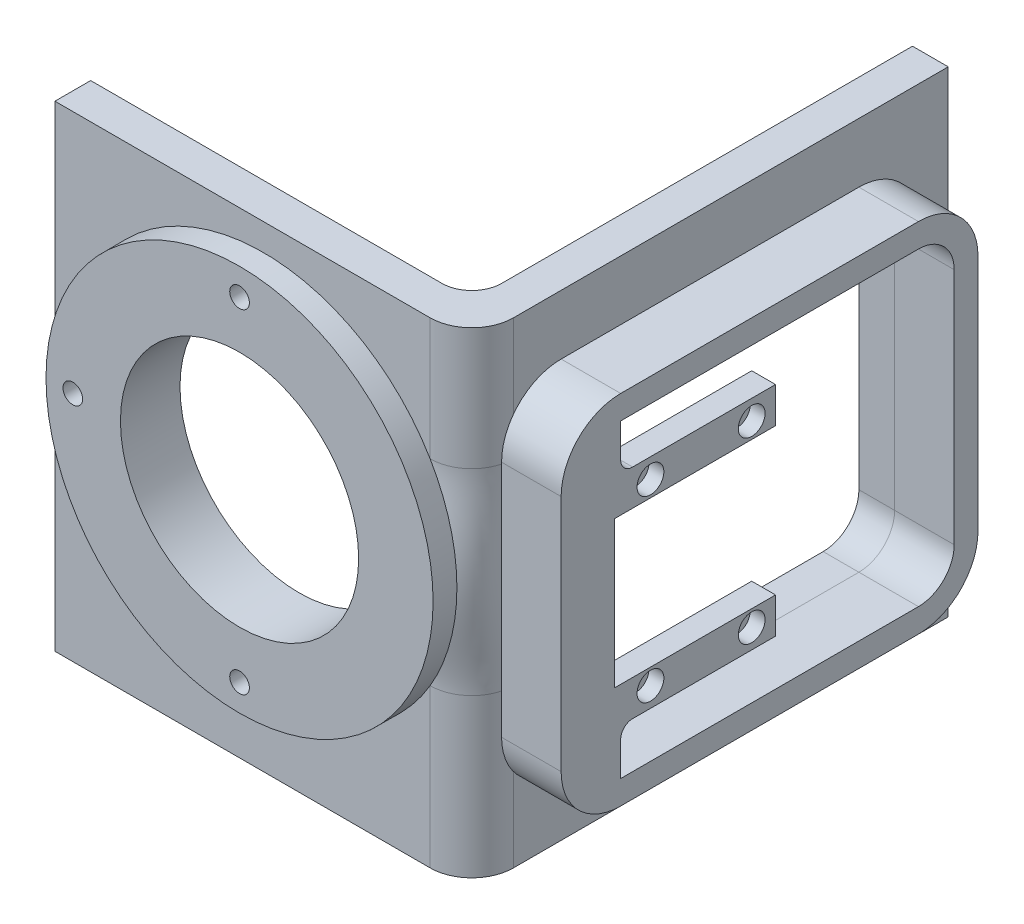
SolidWorks part; units mm, degrees
ref_plane "Front Plane" through (0, 0, 0) normal (0, 0, 1) x (1, 0, 0)
ref_plane "Top Plane" through (0, 0, 0) normal (0, 1, 0) x (1, 0, 0)
ref_plane "Right Plane" through (0, 0, 0) normal (1, 0, 0) x (0, 0, -1)
sketch "Sketch1" plane through (0, 0, 0) normal (0, 0, 1) x (1, 0, 0)
  circle A5 centre (0, 0) radius 32.5
  dimension "D1" = 65
extrude "Boss-Extrude1" add sketch "Sketch1" against normal blind 4
ref_plane "Plane1" through (45, 0, 0) normal (1, 0, 0) x (0, 0, -1)
sketch "Sketch10" plane through (0, 0, -4) normal (0, 0, -1) x (-1, 0, 0)
  line L0 (0, -3) -> (0, 0) construction
  line L1 (-35, -43) -> (35, -43)
  line L2 (-35, -43) -> (-35, 37)
  line L3 (-35, 37) -> (35, 37)
  line L4 (35, -43) -> (35, 37)
  line L5 (-35, -43) -> (35, 37) construction
  line L6 (-35, 37) -> (35, -43) construction
  point P0 (0, -3)
  dimension "D3" = 3
  dimension "D1" = 80
  dimension "D2" = 70
extrude "Boss-Extrude6" add sketch "Sketch10" along normal blind 80
sketch "Sketch2" plane through (45, 0, 0) normal (1, 0, 0) x (0, 0, -1)
  line L2 (0, -3) -> (146.6861, -3) construction
  line L3 (44, -3) -> (44, 30) construction
  line L5 (4, 37) -> (4, -43) construction
  line L6 (84, 37) -> (84, -43) construction
  line L7 (19, -33) -> (69, -33)
  line L8 (9, -23) -> (9, 17)
  line L9 (19, 27) -> (69, 27)
  line L10 (79, -23) -> (79, 17)
  line L11 (9, -33) -> (79, 27) construction
  line L12 (9, 27) -> (79, -33) construction
  arc A1 (19, -33) -> (9, -23) centre (19, -23) cw
  arc A2 (69, -33) -> (79, -23) centre (69, -23) ccw
  arc A3 (69, 27) -> (79, 17) centre (69, 17) cw
  arc A4 (9, 17) -> (19, 27) centre (19, 17) cw
  point P0 (84, -3)
  dimension "D1" = 70
  dimension "D3" = 10
  dimension "D2" = 60
extrude "Boss-Extrude2" add sketch "Sketch2" against normal up to surface (10 mm away) separate body up to face at (35, -3, -44)
sketch "Sketch11" plane through (0, 37, 0) normal (0, 1, 0) x (1, 0, 0)
  line L1 (-35, 84) -> (29, 84)
  line L2 (-35, 84) -> (-35, 10)
  line L3 (-35, 10) -> (29, 10)
  line L4 (29, 84) -> (29, 10)
  dimension "D1" = 74
  dimension "D2" = 64
extrude "Cut-Extrude5" cut sketch "Sketch11" against normal through all
sketch "Sketch4" plane through (35, 0, 0) normal (-1, 0, 0) x (0, 0, 1)
  line L8 (-69, -29) -> (-19, -29)
  line L9 (-75, 17) -> (-75, -23)
  line L10 (-19, 23) -> (-69, 23)
  line L11 (-13, -23) -> (-13, 17)
  line L12 (-69, -29) -> (-19, -29)
  line L13 (-75, 17) -> (-75, -23)
  line L14 (-19, 23) -> (-69, 23)
  line L15 (-13, -23) -> (-13, 17)
  arc A10 (-75, -23) -> (-69, -29) centre (-69, -23) ccw
  arc A11 (-69, 23) -> (-75, 17) centre (-69, 17) ccw
  arc A12 (-13, 17) -> (-19, 23) centre (-19, 17) ccw
  arc A13 (-19, -29) -> (-13, -23) centre (-19, -23) ccw
  arc A14 (-75, -23) -> (-69, -29) centre (-69, -23) ccw
  arc A15 (-69, 23) -> (-75, 17) centre (-69, 17) ccw
  arc A16 (-13, 17) -> (-19, 23) centre (-19, 17) ccw
  arc A17 (-19, -29) -> (-13, -23) centre (-19, -23) ccw
  dimension "D1" = 4
extrude "Cut-Extrude2" cut sketch "Sketch4" against normal through all contours L12 A17 L15 A16 L14 A15 L13 A14 region at (35, -3, -44)
sketch "Sketch5" plane through (45, 0, 0) normal (1, 0, 0) x (0, 0, -1)
  line L0 (48, -3) -> (13, -3) construction
  line L1 (45, 15.3) -> (45, 9.3)
  line L2 (45, 9.3) -> (18, 9.3)
  line L3 (18, 9.3) -> (18, -15.3)
  line L4 (18, -15.3) -> (45, -15.3)
  line L5 (45, -15.3) -> (45, -21.3)
  line L6 (45, -21.3) -> (19, -21.3)
  line L8 (45, 15.3) -> (19, 15.3)
  line L10 (48, -3) -> (48, -18) construction
  line L11 (48, -18) -> (41, -18) construction
  line L12 (41, -18) -> (39, -18) construction
  line L13 (39, -18) -> (24, -18) construction
  line L15 (13, 17) -> (13, -23)
  line L16 (19, 15.3) -> (19, 23)
  line L17 (19, -21.3) -> (19, -29)
  line L18 (13, -23) -> (13, 17) construction
  circle A0 centre (48, -3) radius 11 construction
  arc A1 (19, 23) -> (13, 17) centre (19, 17) ccw construction
  circle A2 centre (41, -18) radius 1.25
  arc A3 (19, 23) -> (13, 17) centre (19, 17) ccw
  circle A6 centre (24, -18) radius 1.25
  circle A7 centre (41, 12) radius 1.25
  circle A9 centre (24, 12) radius 1.25
  arc A10 (13, -23) -> (19, -29) centre (19, -23) ccw
  point P8 (18, -3)
  dimension "D1" = 22
  dimension "D6" = 2.5
  dimension "D3" = 24.6
  dimension "D4" = 15
  dimension "D5" = 7
  dimension "D7" = 17
  dimension "D9" = 6
  dimension "D10" = 5
  dimension "D12" = 3
  dimension "D2" = 30
extrude "Boss-Extrude3" add sketch "Sketch5" against normal blind 4
sketch "Sketch13" plane through (35, 0, 0) normal (1, 0, 0) x (0, 0, -1)
  line L4 (13, 17) -> (13, -23)
  line L5 (19, -29) -> (69, -29)
  line L6 (75, -23) -> (75, 17)
  line L7 (69, 23) -> (19, 23)
  line L8 (13, 17) -> (13, -23)
  line L9 (19, -29) -> (69, -29)
  line L10 (75, -23) -> (75, 17)
  line L11 (69, 23) -> (19, 23)
  arc A6 (19, 23) -> (13, 17) centre (19, 17) ccw
  arc A7 (13, -23) -> (19, -29) centre (19, -23) ccw
  arc A8 (69, -29) -> (75, -23) centre (69, -23) ccw
  arc A9 (75, 17) -> (69, 23) centre (69, 17) ccw
  arc A10 (19, 23) -> (13, 17) centre (19, 17) ccw
  arc A11 (13, -23) -> (19, -29) centre (19, -23) ccw
  arc A12 (69, -29) -> (75, -23) centre (69, -23) ccw
  arc A13 (75, 17) -> (69, 23) centre (69, 17) ccw
  dimension "D1" = 0
extrude "Cut-Extrude6" cut sketch "Sketch13" against normal up to surface (6 mm away) up to face at (29, -3, -47)
sketch "Sketch14" plane through (0, 0, 0) normal (0, 0, 1) x (1, 0, 0)
  circle A2 centre (0, 0) radius 28.5
  circle A3 centre (0, 0) radius 28.5
  dimension "D1" = 4
sketch "Sketch16" plane through (45, 0, 0) normal (1, 0, 0) x (0, 0, -1)
  circle A0 centre (41, -18) radius 2.25
  circle A2 centre (24, -18) radius 2.25
  circle A3 centre (24, 12) radius 2.25
  circle A5 centre (41, 12) radius 2.25
  dimension "D1" = 4.5
extrude "Cut-Extrude8" cut sketch "Sketch16" against normal blind 2.5
fillet "Fillet1" radius 7 1 edges at (35, -3, -4)
fillet "Fillet2" [suppressed] radius 10
sketch "Sketch17" plane through (0, 0, -10) normal (0, 0, -1) x (-1, 0, 0)
  line L0 (-28, 0) -> (0, 0) construction
  line L1 (0, 28) -> (0, 0) construction
  line L2 (28, 0) -> (0, 0) construction
  line L3 (0, -28) -> (0, 0) construction
  circle A0 centre (-28, 0) radius 1.65 construction
  circle A1 centre (0, 28) radius 1.65
  circle A2 centre (28, 0) radius 1.65
  circle A3 centre (0, -28) radius 1.65
  point P10 (0, 0)
  point P17 (0, 0)
  dimension "D4" = 3.3
  dimension "D3" = 28
  dimension "D1" = 4
  dimension "D2" = 4
extrude "Cut-Extrude9" cut sketch "Sketch17" against normal through all
sketch "Sketch19" plane through (29, 0, 0) normal (-1, 0, 0) x (0, 0, 1)
  line L0 (-76, 37) -> (-76, -43) construction
  line L1 (-10, 37) -> (-84, 37) construction
  line L2 (-10, -43) -> (-84, -43) construction
  line L3 (-84, -43) -> (-84, 37) construction
  line L4 (-76, 30) -> (-78, 30)
  line L5 (-76, 30) -> (-76, 25.8)
  line L6 (-76, 25.8) -> (-78, 25.8)
  line L7 (-78, 30) -> (-78, 25.8)
  line L8 (-76, -31.8) -> (-78, -31.8)
  line L9 (-76, -31.8) -> (-76, -36)
  line L10 (-76, -36) -> (-78, -36)
  line L11 (-78, -31.8) -> (-78, -36)
  line L12 (-76, -3) -> (-84, -3) construction
  dimension "D1" = 8
  dimension "D2" = 7
  dimension "D3" = 2
  dimension "D4" = 4.2
extrude "Cut-Extrude10" cut sketch "Sketch19" along direction (1, 0, 0) on the side against the normal blind 4.8
sketch "Sketch21" plane through (0, 0, -10) normal (0, 0, -1) x (-1, 0, 0)
  line L0 (27, 37) -> (27, -43) construction
  line L1 (29, 30) -> (27, 30)
  line L2 (29, 30) -> (29, 25.8)
  line L3 (29, 25.8) -> (27, 25.8)
  line L4 (27, 30) -> (27, 25.8)
  line L5 (29, -31.8) -> (27, -31.8)
  line L6 (29, -31.8) -> (29, -36)
  line L7 (29, -36) -> (27, -36)
  line L8 (27, -31.8) -> (27, -36)
  line L9 (27, -3) -> (35, -3) construction
  line L10 (35, -43) -> (35, 37) construction
  line L11 (35, 37) -> (-29, 37) construction
  dimension "D1" = 2
  dimension "D2" = 4.2
  dimension "D3" = 7
  dimension "D4" = 8
extrude "Cut-Extrude11" cut sketch "Sketch21" against normal blind 4.8
sketch "Sketch22" plane through (0, 0, -84) normal (0, 0, -1) x (-1, 0, 0)
  line L0 (-29, 30) -> (-33.8, 25.8) construction
  line L1 (-29, -31.8) -> (-33.8, -36) construction
  line L4 (-29, 25.8) -> (-29, 30)
  line L5 (-29, 30) -> (-33.8, 30)
  line L6 (-33.8, 30) -> (-33.8, 25.8)
  line L7 (-33.8, 25.8) -> (-29, 25.8)
  line L8 (-29, 25.8) -> (-29, 30) construction
  line L9 (-29, 30) -> (-33.8, 30) construction
  line L11 (-33.8, 25.8) -> (-29, 25.8) construction
  line L12 (-29, -36) -> (-29, -31.8)
  line L13 (-29, -31.8) -> (-33.8, -31.8)
  line L14 (-33.8, -31.8) -> (-33.8, -36)
  line L15 (-33.8, -36) -> (-29, -36)
  line L16 (-29, -36) -> (-29, -31.8) construction
  line L17 (-29, -31.8) -> (-33.8, -31.8) construction
  line L19 (-33.8, -36) -> (-29, -36) construction
  line L22 (-33.8, 30) -> (-33.8, 25.8)
  line L23 (-33.8, -31.8) -> (-33.8, -36)
  circle A0 centre (-31.4, 27.9) radius 1.15
  circle A1 centre (-31.4, -33.9) radius 1.15
  dimension "D3" = 2.3
  dimension "D1" = 0
  dimension "D2" = 0
extrude "Cut-Extrude12" cut sketch "Sketch22" against normal up to surface (6 mm away) contours A0 | A1 region at (31.4, 27.9, -84) region at (31.4, -33.9, -84) up to face at (31.4, 27.9, -78)
sketch "Sketch23" plane through (-35, 0, 0) normal (-1, 0, 0) x (0, 0, 1)
  line L0 (-10, -36) -> (-5.2, -31.8) construction
  line L1 (-10, 25.8) -> (-5.2, 30) construction
  line L4 (-10, -31.8) -> (-10, -36)
  line L5 (-10, -36) -> (-5.2, -36)
  line L6 (-5.2, -36) -> (-5.2, -31.8)
  line L7 (-5.2, -31.8) -> (-10, -31.8)
  line L8 (-10, -31.8) -> (-10, -36) construction
  line L9 (-10, -36) -> (-5.2, -36) construction
  line L10 (-5.2, -36) -> (-5.2, -31.8) construction
  line L11 (-5.2, -31.8) -> (-10, -31.8) construction
  line L12 (-10, 30) -> (-10, 25.8)
  line L13 (-10, 25.8) -> (-5.2, 25.8)
  line L14 (-5.2, 25.8) -> (-5.2, 30)
  line L15 (-5.2, 30) -> (-10, 30)
  line L16 (-10, 30) -> (-10, 25.8) construction
  line L17 (-10, 25.8) -> (-5.2, 25.8) construction
  line L18 (-5.2, 25.8) -> (-5.2, 30) construction
  line L19 (-5.2, 30) -> (-10, 30) construction
  circle A0 centre (-7.6, -33.9) radius 1.15
  circle A1 centre (-7.6, 27.9) radius 1.15
  dimension "D3" = 2.3
  dimension "D1" = 0
  dimension "D2" = 0
extrude "Cut-Extrude13" cut sketch "Sketch23" against normal up to surface (6 mm away) up to face at (-29, -33.9, -7.6)
sketch "Sketch24" plane through (0, 0, -10) normal (0, 0, -1) x (-1, 0, 0)
  circle A0 centre (0, 0) radius 20
  dimension "D1" = 40
extrude "Cut-Extrude14" cut sketch "Sketch24" against normal up to surface (10 mm away) up to face at (-1.65, 28, 0)
fillet "Fillet4" radius 5 1 edges at (29, -3, -10)
fillet "Fillet5" radius 2 2 edges at (43, -21.3, -19) (43, 15.3, -19)
